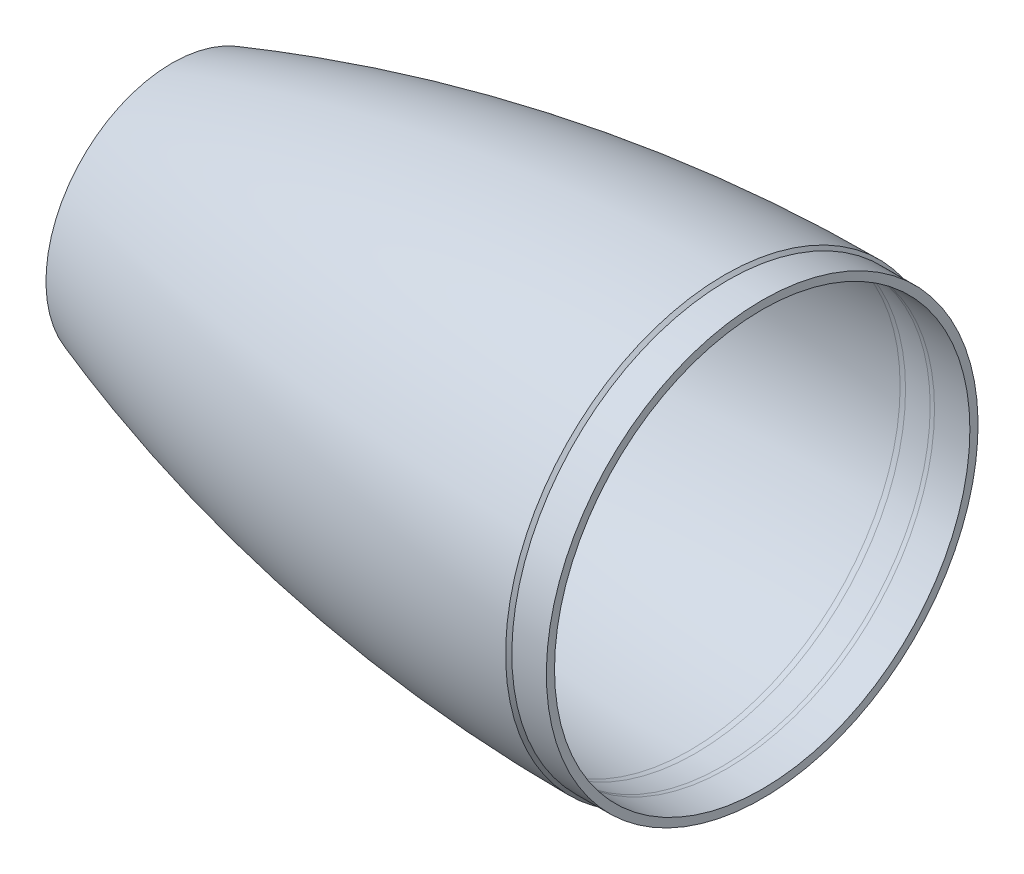
SolidWorks part; units mm, degrees
ref_plane "Front Plane" through (0, 0, 0) normal (0, 0, 1) x (1, 0, 0)
ref_plane "Top Plane" through (0, 0, 0) normal (0, 1, 0) x (1, 0, 0)
ref_plane "Right Plane" through (0, 0, 0) normal (1, 0, 0) x (0, 0, -1)
sketch "Sketch1" plane through (0, 0, 0) normal (0, 0, 1) x (1, 0, 0)
  line L4 (0, 0) -> (-304.8, 0) construction
  line L9 (0, 76.3778) -> (0, 0) construction
  line L10 (0, 80.518) -> (50.8, 80.518) construction
  line L11 (-203.2, 46.355) -> (-203.2, 41.4655)
  line L12 (-203.2, 41.4655) -> (-181.891, 41.4655)
  line L13 (-174.0697, 43.1452) -> (-128.9003, 63.4837)
  line L15 (1.143, 79.375) -> (13.843, 79.375)
  line L16 (0, 80.518) -> (1.143, 79.375)
  line L17 (0.8317, 76.3778) -> (13.843, 76.3778)
  line L18 (13.843, 76.3778) -> (13.843, 79.375)
  line L19 (-0.8286, 76.4503) -> (-10.7639, 77.3195)
  arc A4 (0, 80.518) -> (-203.2, 46.355) centre (0, -540.8758) ccw
  arc A5 (-12.8191, 77.3879) -> (-124.9274, 64.7705) centre (0, -540.8758) ccw
  arc A6 (0, 77.5208) -> (-202.2199, 43.5226) centre (0, -540.8758) ccw construction
  arc A7 (-174.0697, 43.1452) -> (-181.891, 41.4655) centre (-181.891, 60.5155) cw
  arc A8 (-128.9003, 63.4837) -> (-124.9274, 64.7705) centre (-121.079, 46.1133) cw
  arc A9 (-10.7639, 77.3195) -> (-12.8191, 77.3879) centre (-12.4242, 58.342) ccw
  arc A10 (-0.8286, 76.4503) -> (0.8317, 76.3778) centre (0.8317, 95.4278) ccw
  point P8 (-57.2734, -19.8104)
  point P9 (0, 313.4439)
  point P10 (-150.9565, 274.6984)
  point P21 (-177.8, 41.4655)
  point P24 (-127, 64.3393)
  dimension "D7" = 25.4
  dimension "D10" = 19.05
  dimension "D11" = 19.05
  dimension "D17" = 19.05
  dimension "D1" = 161.036
  dimension "D2" = 50.8
  dimension "D3" = 203.2
  dimension "D4" = 92.71
  dimension "D6" = 82.931
  dimension "D8" = 50.8
  dimension "D9" = 304.8
  dimension "D12" = 12.7
  dimension "D13" = 158.75
  dimension "D14" = 45
  dimension "D15" = 2.9972
  dimension "D16" = 175
  dimension "D5" = 2.9972
revolve "Revolve1" add sketch "Sketch1" angle 360 about L4
